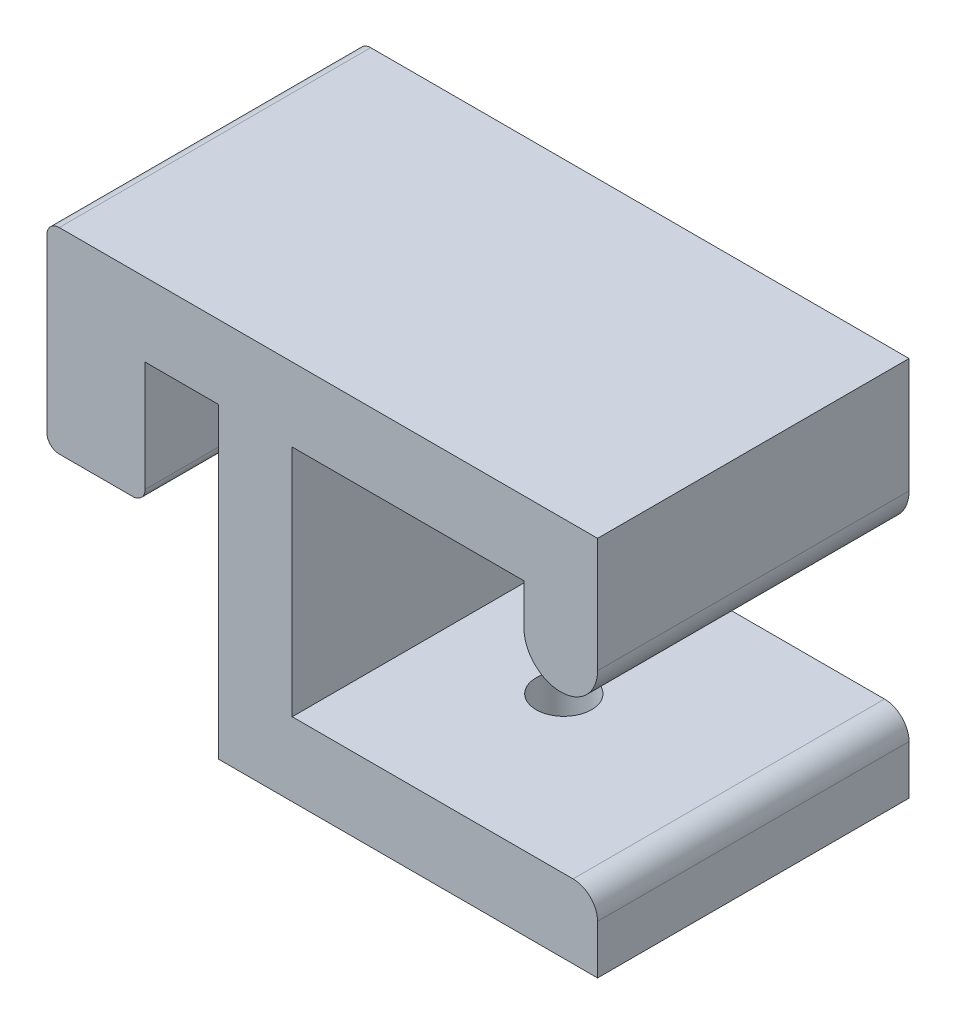
SolidWorks part; units mm, degrees
ref_plane "Front Plane" through (0, 0, 0) normal (0, 0, 1) x (1, 0, 0)
ref_plane "Top Plane" through (0, 0, 0) normal (0, 1, 0) x (1, 0, 0)
ref_plane "Right Plane" through (0, 0, 0) normal (1, 0, 0) x (0, 0, -1)
sketch "Sketch1" plane through (0, 0, 0) normal (0, 0, 1) x (1, 0, 0)
  line L2 (-146.8124, 5.1981) -> (-162.2624, 5.1981)
  line L3 (-162.2624, 5.1981) -> (-162.2624, -10.3269)
  line L4 (-162.2624, -10.3269) -> (-146.8124, -10.3269)
  line L5 (-146.8124, -10.3269) -> (-146.8124, -7.3269)
  line L6 (-146.8124, -7.3269) -> (-159.2624, -7.3269)
  line L7 (-159.2624, -7.3269) -> (-159.2624, 2.1981)
  line L9 (-159.2624, 2.1981) -> (-149.8124, 2.1981)
  line L12 (-159.2624, 2.1981) -> (-159.2624, -0.9769) construction
  line L13 (43.9376, 2.1981) -> (31.2376, 2.1981) construction
  line L14 (-146.8124, 5.1981) -> (-146.8124, 2.1981)
  line L15 (43.9376, 2.1981) -> (31.2376, 2.1981) construction
  line L18 (-149.8124, 2.1981) -> (-149.8124, 0.5231)
  line L19 (-146.8124, 2.1981) -> (-146.8124, 0.5231)
  line L20 (43.9376, -0.9769) -> (31.2376, -0.9769) construction
  line L21 (-141.4824, -7.3269) -> (26.1576, -7.3269) construction
  line L22 (26.1576, 2.1981) -> (-141.4824, 2.1981) construction
  line L24 (-149.8124, 2.1981) -> (-149.8124, -0.9769) construction
  arc A4 (-149.8124, 0.5231) -> (-146.8124, 0.5231) centre (-148.3124, 0.5231) ccw
  dimension "D4" = 3
  dimension "D1" = 3
  dimension "D2" = 3
  dimension "D3" = 3
extrude "MainBody" add sketch "Sketch1" along normal blind 12.7
hole_wizard "#4-40 Tapped Hole1" positions "Sketch3" profile "Sketch4" tap size "#4-40" standard "ANSI Inch" end condition up to next
sketch "Sketch3" plane through (0, -10.3269, 0) normal (0, -1, 0) x (-1, 0, 0)
  line L0 (162.2624, -12.7) -> (146.8124, -12.7) construction
  line L1 (146.8124, -12.7) -> (146.8124, 0) construction
  point P2 (154.5374, -6.35)
  point P6 (154.5374, -12.7)
  point P9 (146.8124, -6.35)
sketch "Sketch4" plane through (-154.5374, -10.3269, 6.35) normal (1, 0, 0) x (0, 0, -1)
  line L0 (0, 0) -> (0, 3)
  line L1 (0, 3) -> (1.1303, 3)
  line L2 (1.1303, 3) -> (1.1303, 0)
  line L5 (1.1303, 0) -> (0, 0)
  line L11 (0, -6.35) -> (0, 107.95) construction
  dimension "Thru Tap Drill Dia." = 2.2606
  dimension "Thru Tap Drill Depth" = 3
cosmetic thread "Hole Thread3" parameters "D1"=6.35, "D2"=2.8448
fillet "Fillet4" radius 1 1 edges at (-146.8124, -7.3269, 6.35)
sketch "Sketch6" plane through (0, 0, 12.7) normal (0, 0, 1) x (1, 0, 0)
  line L0 (-162.2624, 5.1981) -> (-168.7624, 5.1981)
  line L1 (-162.2624, 5.1981) -> (-162.2624, -10.3269) construction
  line L6 (-162.2624, 2.1981) -> (-162.2624, 5.1981)
  line L7 (-169.2624, 4.6981) -> (-169.2624, -2.3019)
  line L8 (-168.7624, -2.8019) -> (-165.7624, -2.8019)
  line L9 (-165.2624, -2.3019) -> (-165.2624, 2.1981)
  line L10 (-165.2624, 2.1981) -> (-162.2624, 2.1981)
  line L12 (-146.8124, 5.1981) -> (-162.2624, 5.1981) construction
  line L13 (-159.2624, 2.1981) -> (-149.8124, 2.1981) construction
  arc A4 (-165.7624, -2.8019) -> (-165.2624, -2.3019) centre (-165.7624, -2.3019) ccw
  arc A5 (-169.2624, -2.3019) -> (-168.7624, -2.8019) centre (-168.7624, -2.3019) ccw
  arc A6 (-168.7624, 5.1981) -> (-169.2624, 4.6981) centre (-168.7624, 4.6981) ccw
  point P11 (-165.2624, -2.8019)
  point P15 (-169.2624, -2.8019)
  dimension "D5" = 0.5
  dimension "D3" = 3
  dimension "D1" = 3
extrude "Hook" add sketch "Sketch6" against normal up to surface (12.7 mm away) up to face at (-152.5027, -2.6444, 0)
equation "\"HookThicknes\"= 5"
equation "\"HookThickness\"=5"
equation "\"HookOverhang\"=3"
equation "\"D3@Sketch6\"=\"HookOverhang\""
equation "\"HookHeight\"=5"
